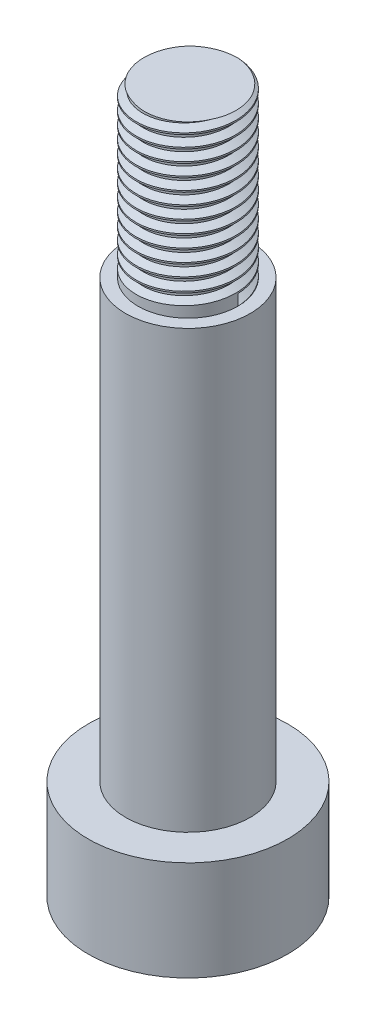
SolidWorks part; units mm, degrees
ref_plane "前视基准面" through (0, 0, 0) normal (0, 0, 1) x (1, 0, 0)
ref_plane "上视基准面" through (0, 0, 0) normal (0, 1, 0) x (1, 0, 0)
ref_plane "右视基准面" through (0, 0, 0) normal (1, 0, 0) x (0, 0, -1)
sketch "草图1" plane through (0, 0, 0) normal (0, 1, 0) x (1, 0, 0)
  circle A0 centre (0, 0) radius 5
  dimension "D1" = 10
extrude "凸台-拉伸1" add sketch "草图1" along normal blind 35
sketch "草图2" plane through (0, 35, 0) normal (0, 1, 0) x (1, 0, 0)
  circle A0 centre (0, 0) radius 4
  dimension "D1" = 8
extrude "凸台-拉伸2" add sketch "草图2" along normal blind 13.25
thread "螺纹线1" pitch 1 method cut profile "螺纹线轮廓1" start angle 0, offset 0, length 15, pitch 1, diameter 8
ref_plane "基准面1" through (4, 35, 0) normal (0, 0, 1) x (1, 0, 0)
sketch "螺纹线轮廓1" plane through (4, 35, 0) normal (0, 0, 1) x (1, 0, 0)
  line L0 (0, 0) -> (0, 1) construction
  line L11 (0, 0) -> (0, 0.875)
  line L12 (0, 0.875) -> (-0.5413, 0.5625)
  line L13 (-0.5413, 0.5625) -> (-0.5413, 0.3125)
  line L15 (-0.5413, 0.3125) -> (0, 0)
  line L17 (-0.5413, 0.4375) -> (0, 0.4375) construction
  point P2 (0, 0)
  dimension "Pitch" = 1
  dimension "Profile_Angle" = 60
  dimension "Profile_Land" = 0.25
  dimension "Profile_Height" = 0.5413
sketch "草图7" plane through (0, 0, 0) normal (0, -1, 0) x (-1, 0, 0)
  circle A0 centre (0, 0) radius 8
  dimension "D1" = 16
extrude "凸台-拉伸3" add sketch "草图7" along normal blind 8
